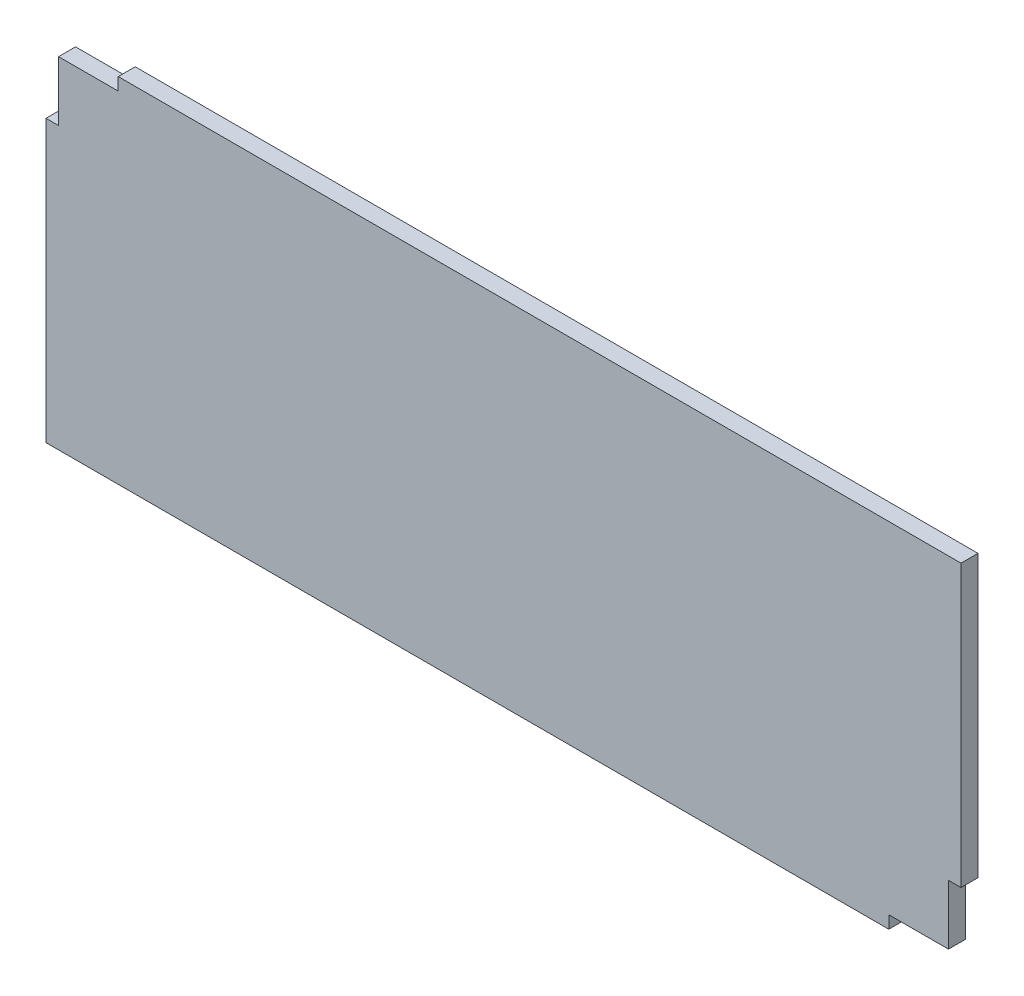
SolidWorks part; units mm, degrees
ref_plane "Front Plane" through (0, 0, 0) normal (0, 0, 1) x (1, 0, 0)
ref_plane "Top Plane" through (0, 0, 0) normal (0, 1, 0) x (1, 0, 0)
ref_plane "Right Plane" through (0, 0, 0) normal (1, 0, 0) x (0, 0, -1)
sketch "Sketch1" plane through (0, 0, 0) normal (0, 0, 1) x (1, 0, 0)
  line L0 (27, 132) -> (27, 127.3)
  line L5 (27, 127.3) -> (4.7, 127.3)
  line L6 (4.7, 127.3) -> (4.7, 105)
  line L7 (4.7, 105) -> (0, 105)
  line L8 (342, 27) -> (337.3, 27)
  line L9 (337.3, 27) -> (337.3, 4.7)
  line L10 (337.3, 4.7) -> (315, 4.7)
  line L11 (315, 4.7) -> (315, 0)
  line L12 (342, 132) -> (342, 27)
  line L13 (315, 0) -> (0, 0)
  line L14 (0, 0) -> (0, 105)
  line L15 (342, 132) -> (27, 132)
  dimension "D1" = 342
  dimension "D2" = 132
  dimension "D3" = 4.7
  dimension "D4" = 4.7
  dimension "D5" = 27
  dimension "D6" = 27
  dimension "D7" = 4.7
  dimension "D8" = 4.7
  dimension "D9" = 27
  dimension "D10" = 27
extrude "Boss-Extrude1" add sketch "Sketch1" along normal blind 6.35
